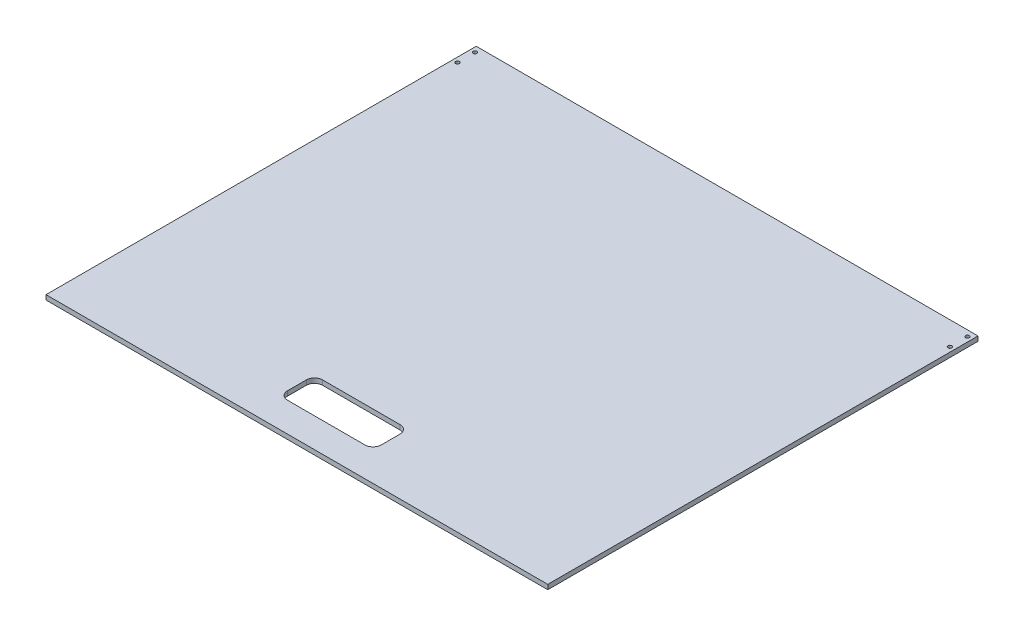
SolidWorks part; units mm, degrees
ref_plane "Front Plane" through (0, 0, 0) normal (0, 0, 1) x (1, 0, 0)
ref_plane "Top Plane" through (0, 0, 0) normal (0, 1, 0) x (1, 0, 0)
ref_plane "Right Plane" through (0, 0, 0) normal (1, 0, 0) x (0, 0, -1)
sketch "Sketch1" plane through (0, 0, 0) normal (0, 1, 0) x (1, 0, 0)
  line L1 (-214, -183.5) -> (214, -183.5)
  line L2 (-214, -183.5) -> (-214, 183.5)
  line L3 (-214, 183.5) -> (214, 183.5)
  line L4 (214, -183.5) -> (214, 183.5)
  line L5 (-214, -183.5) -> (214, 183.5) construction
  line L6 (-214, 183.5) -> (214, -183.5) construction
  point P0 (0, 0)
  dimension "D1" = 428
  dimension "D2" = 367
extrude "Boss-Extrude1" add sketch "Sketch1" along normal blind 4
sketch "Sketch2" plane through (0, 0, 0) normal (0, -1, 0) x (1, 0, 0)
  line L0 (214, -183.5) -> (-214, -183.5) construction
  line L1 (214, 183.5) -> (214, -183.5) construction
  circle A0 centre (210, -163.5) radius 1.6
  circle A1 centre (210, -178.5) radius 1.6
  dimension "D1" = 5
  dimension "D3" = 3.2
  dimension "D2" = 15
  dimension "D4" = 4
extrude "Cut-Extrude1" cut sketch "Sketch2" against normal through all
mirror "Mirror1" about plane through (0, 0, 0) normal (1, 0, 0) of "Cut-Extrude1"
sketch "Sketch3" plane through (0, 4, 0) normal (0, 1, 0) x (1, 0, 0)
  line L0 (-214, -183.5) -> (214, -183.5) construction
  line L1 (-33, -158.5) -> (33, -158.5)
  line L2 (-40, -151.5) -> (-40, -135.5)
  line L3 (-33, -128.5) -> (33, -128.5)
  line L4 (40, -151.5) -> (40, -135.5)
  line L5 (-40, -158.5) -> (40, -128.5) construction
  line L6 (-40, -128.5) -> (40, -158.5) construction
  arc A0 (-40, -135.5) -> (-33, -128.5) centre (-33, -135.5) cw
  arc A1 (-33, -158.5) -> (-40, -151.5) centre (-33, -151.5) cw
  arc A2 (33, -158.5) -> (40, -151.5) centre (33, -151.5) ccw
  arc A3 (33, -128.5) -> (40, -135.5) centre (33, -135.5) cw
  point P0 (0, -143.5)
  dimension "D4" = 7
  dimension "D1" = 25
  dimension "D2" = 80
  dimension "D3" = 30
extrude "Cut-Extrude2" cut sketch "Sketch3" against normal through all
